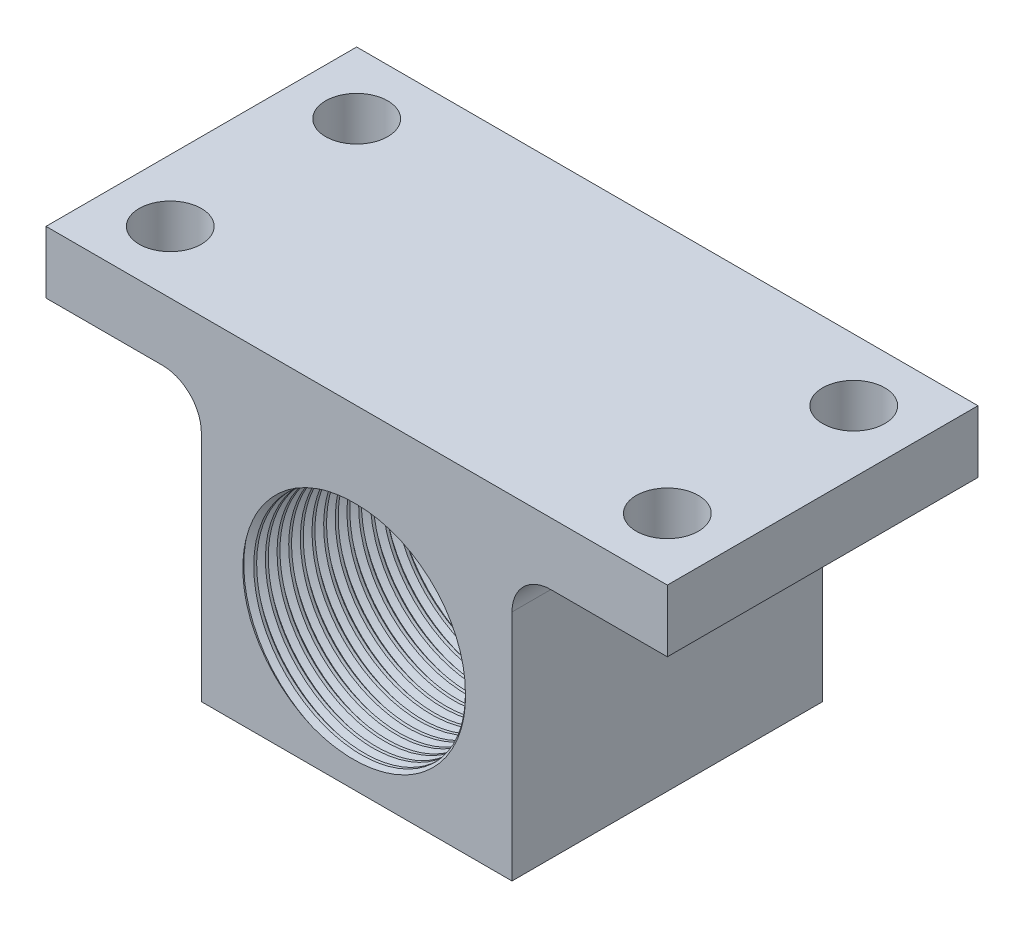
SolidWorks part; units mm, degrees
ref_plane "Ön Düzlem" through (0, 0, 0) normal (0, 0, 1) x (1, 0, 0)
ref_plane "Üst Düzlem" through (0, 0, 0) normal (0, 1, 0) x (1, 0, 0)
ref_plane "Sağ Düzlem" through (0, 0, 0) normal (1, 0, 0) x (0, 0, -1)
sketch "Çizim1" plane through (0, 0, 0) normal (0, 0, 1) x (1, 0, 0)
  line L0 (-17.0008, 10.7368) -> (-37.0008, 10.7368)
  line L2 (-17.0008, 10.7368) -> (-17.0008, -24.2632)
  line L3 (-17.0008, -24.2632) -> (22.9992, -24.2632)
  line L4 (22.9992, 10.7368) -> (22.9992, -24.2632)
  line L5 (42.9992, 10.7368) -> (22.9992, 10.7368)
  line L6 (42.9992, 10.7368) -> (42.9992, 18.7368)
  line L7 (42.9992, 18.7368) -> (-37.0008, 18.7368)
  line L8 (-37.0008, 10.7368) -> (-37.0008, 18.7368)
  circle A0 centre (2.9992, -6.2632) radius 14
  dimension "D3" = 28
  dimension "D1" = 35
  dimension "D2" = 40
  dimension "D4" = 8
  dimension "D5" = 80
  dimension "D6" = 20
  dimension "D7" = 25
extrude "Yükseklik-Ekstrüzyon1" add sketch "Çizim1" along normal blind 40
sketch "Çizim2" plane through (0, 18.7368, 0) normal (0, 1, 0) x (1, 0, 0)
  circle A0 centre (-29.0008, -8) radius 4
  circle A1 centre (-29.0008, -32) radius 4
  circle A2 centre (34.9992, -32) radius 4
  circle A3 centre (34.9992, -8) radius 4
  dimension "D5" = 8
  dimension "D6" = 8
  dimension "D7" = 8
  dimension "D8" = 8
extrude "Kes-Ekstrüzyon1" cut sketch "Çizim2" against normal blind 40
fillet "Radyus1" radius 5 2 edges at (22.9992, 10.7368, 20) (-17.0008, 10.7368, 20)
thread "Thread1" pitch 1.5 method cut profile "Thread Profile1" start angle 0, offset 5, length 0, pitch 1.5, diameter 28
ref_plane "Plane1" through (16.9992, -6.2632, -5) normal (0, -1, 0) x (1, 0, 0)
sketch "Thread Profile1" plane through (16.9992, -6.2632, -5) normal (0, -1, 0) x (1, 0, 0)
  line L0 (0, 0) -> (0, 1.5) construction
  line L1 (0, 0) -> (0.8119, 0.4687)
  line L2 (0.8119, 0.4687) -> (0.8119, 0.6562)
  line L3 (0.8119, 0.6562) -> (0, 1.125)
  line L4 (0.8119, 0.5625) -> (0, 0.5625) construction
  line L11 (0, 0) -> (0, 1.125)
  point P2 (0, 0)
  dimension "Pitch" = 1.5
  dimension "Profile_Angle" = 60
  dimension "Profile_Land" = 0.1875
  dimension "Profile_Height" = 0.8119
